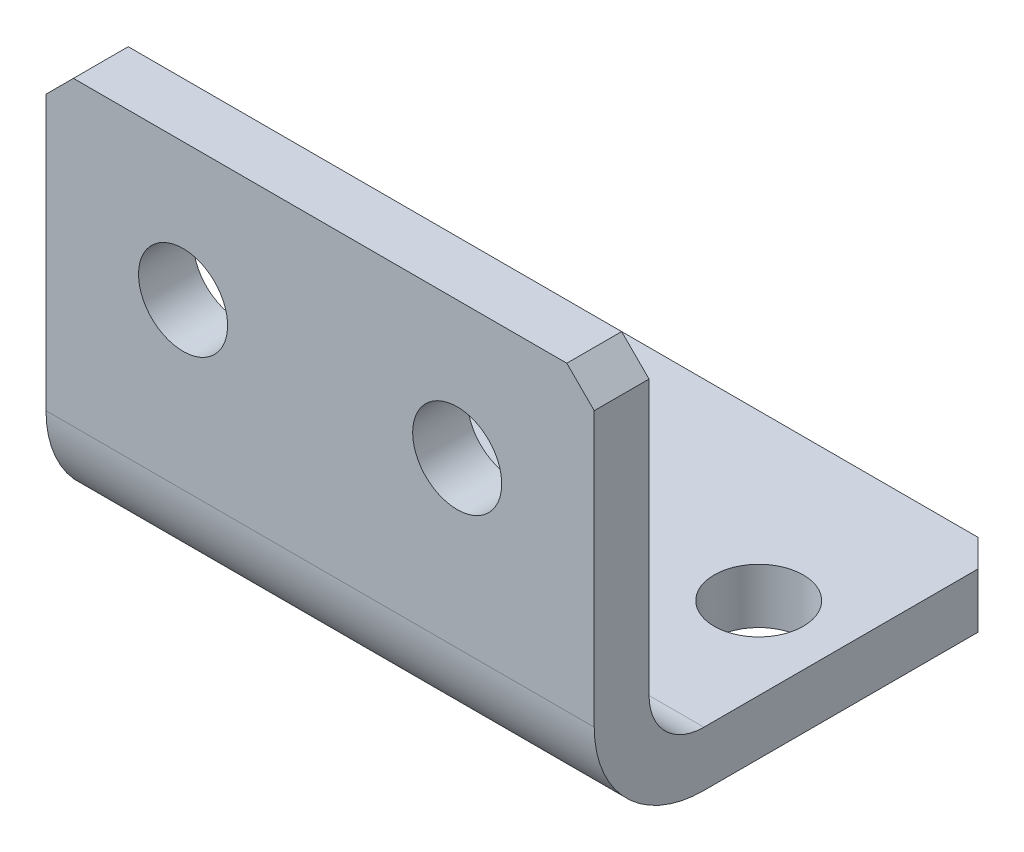
SolidWorks part; units mm, degrees
ref_plane "正面" through (0, 0, 0) normal (0, 0, 1) x (1, 0, 0)
ref_plane "平面" through (0, 0, 0) normal (0, 1, 0) x (1, 0, 0)
ref_plane "右側面" through (0, 0, 0) normal (1, 0, 0) x (0, 0, -1)
ref_plane "平面1" through (0, 0, 0) normal (1, 0, 0) x (0, 0, -1)
sketch "ｽｹｯﾁ1" plane through (0, 0, 0) normal (1, 0, 0) x (0, 0, -1)
  line L0 (8, 0) -> (30, 0)
  line L1 (30, 0) -> (30, 4)
  line L2 (30, 4) -> (8, 4)
  line L3 (4, 8) -> (4, 30)
  line L4 (4, 30) -> (0, 30)
  line L5 (0, 30) -> (0, 8)
  arc A0 (0, 8) -> (8, 0) centre (8, 8) ccw
  arc A1 (8, 4) -> (4, 8) centre (8, 8) cw
extrude "ﾎﾞｽ - 押し出し1" add sketch "ｽｹｯﾁ1" against normal blind 20 and the other way blind 20
ref_plane "平面2" through (0, 0, 0) normal (0, 0, 1) x (1, 0, 0)
sketch "ｽｹｯﾁ2" plane through (0, 0, 0) normal (0, 0, 1) x (1, 0, 0)
  line L0 (-22, 32) -> (-22, 27)
  line L1 (-22, 27) -> (-20, 27)
  line L2 (-20, 27) -> (-20, 28)
  line L3 (-20, 28) -> (-18, 30)
  line L4 (-18, 30) -> (18, 30)
  line L5 (18, 30) -> (20, 28)
  line L6 (20, 28) -> (20, 27)
  line L7 (20, 27) -> (22, 27)
  line L8 (22, 27) -> (22, 32)
  line L9 (22, 32) -> (-22, 32)
extrude "ｶｯﾄ - 押し出し1" cut sketch "ｽｹｯﾁ2" against normal blind 4
ref_plane "平面3" through (0, 0, 0) normal (0, 1, 0) x (1, 0, 0)
sketch "ｽｹｯﾁ3" plane through (0, 0, 0) normal (0, 1, 0) x (1, 0, 0)
  line L0 (-22, 32) -> (-22, 27)
  line L1 (-22, 27) -> (-20, 27)
  line L2 (-20, 27) -> (-20, 28)
  line L3 (-20, 28) -> (-18, 30)
  line L4 (-18, 30) -> (18, 30)
  line L5 (18, 30) -> (20, 28)
  line L6 (20, 28) -> (20, 27)
  line L7 (20, 27) -> (22, 27)
  line L8 (22, 27) -> (22, 32)
  line L9 (22, 32) -> (-22, 32)
extrude "ｶｯﾄ - 押し出し2" cut sketch "ｽｹｯﾁ3" along normal blind 4
ref_plane "平面4" through (0, 20, 0) normal (0, 1, 0) x (1, 0, 0)
sketch "ｽｹｯﾁ4" plane through (0, 20, 0) normal (0, 1, 0) x (1, 0, 0)
  line L0 (10, 9) -> (13.25, 9)
  line L1 (13.25, 9) -> (13.25, 0)
  line L2 (13.25, 0) -> (10, 0)
  line L3 (10, 0) -> (10, 9)
  line L4 (10, 0) -> (10, 9) construction
revolve "ｶｯﾄ - 回転1" cut sketch "ｽｹｯﾁ4" angle 360 about L4 reverse direction yes
ref_plane "平面5" through (0, 20, 0) normal (0, 1, 0) x (1, 0, 0)
sketch "ｽｹｯﾁ5" plane through (0, 20, 0) normal (0, 1, 0) x (1, 0, 0)
  line L0 (-10, 9) -> (-6.75, 9)
  line L1 (-6.75, 9) -> (-6.75, 0)
  line L2 (-6.75, 0) -> (-10, 0)
  line L3 (-10, 0) -> (-10, 9)
  line L4 (-10, 0) -> (-10, 9) construction
revolve "ｶｯﾄ - 回転2" cut sketch "ｽｹｯﾁ5" angle 360 about L4 reverse direction yes
ref_plane "平面6" through (0, 0, -18) normal (0, 0, 1) x (1, 0, 0)
sketch "ｽｹｯﾁ6" plane through (0, 0, -18) normal (0, 0, 1) x (1, 0, 0)
  line L0 (14, 9) -> (17.25, 9)
  line L1 (17.25, 9) -> (17.25, 0)
  line L2 (17.25, 0) -> (14, 0)
  line L3 (14, 0) -> (14, 9)
  line L4 (14, 0) -> (14, 9) construction
revolve "ｶｯﾄ - 回転3" cut sketch "ｽｹｯﾁ6" angle 360 about L4 reverse direction yes
ref_plane "平面7" through (0, 0, -18) normal (0, 0, 1) x (1, 0, 0)
sketch "ｽｹｯﾁ7" plane through (0, 0, -18) normal (0, 0, 1) x (1, 0, 0)
  line L0 (-14, 9) -> (-10.75, 9)
  line L1 (-10.75, 9) -> (-10.75, 0)
  line L2 (-10.75, 0) -> (-14, 0)
  line L3 (-14, 0) -> (-14, 9)
  line L4 (-14, 0) -> (-14, 9) construction
revolve "ｶｯﾄ - 回転4" cut sketch "ｽｹｯﾁ7" angle 360 about L4 reverse direction yes
